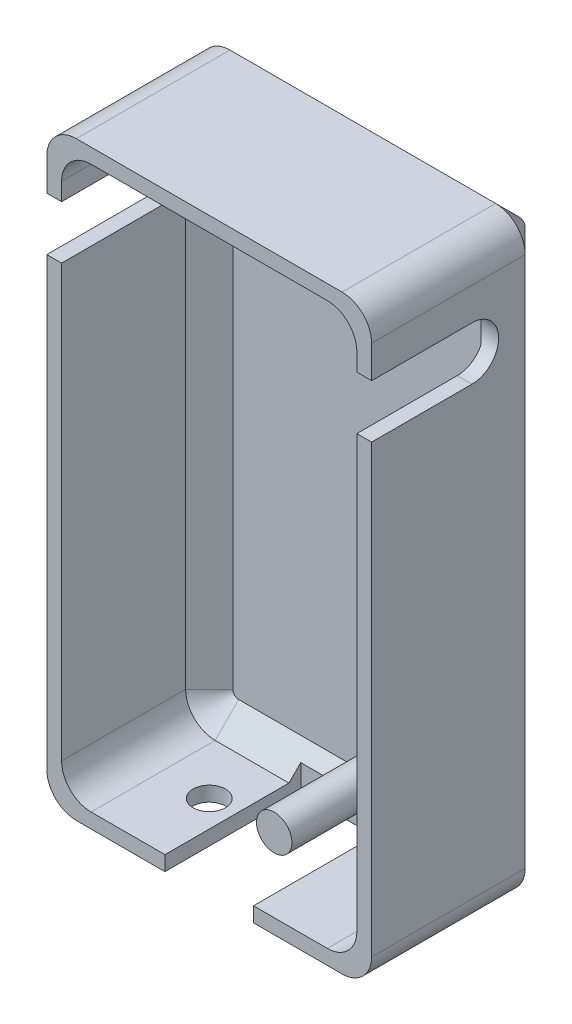
SolidWorks part; units mm, degrees
material "ABS"
ref_plane "前基準面" through (0, 0, 0) normal (0, 0, 1) x (1, 0, 0)
ref_plane "上基準面" through (0, 0, 0) normal (0, 1, 0) x (1, 0, 0)
ref_plane "右基準面" through (0, 0, 0) normal (1, 0, 0) x (0, 0, -1)
sketch "草圖1" plane through (0, 0, 0) normal (0, 0, 1) x (1, 0, 0)
  line L1 (-27.5, -50) -> (27.5, -50)
  line L2 (-27.5, -50) -> (-27.5, 50)
  line L3 (-27.5, 50) -> (27.5, 50)
  line L4 (27.5, -50) -> (27.5, 50)
  line L5 (0, 50) -> (0, -50) construction
  line L6 (-27.5, 0) -> (27.5, 0) construction
  point P0 (0, 0)
  dimension "D1" = 55
  dimension "D2" = 100
extrude "填料-伸長1" add sketch "草圖1" along normal blind 30
sketch "草圖2" plane through (-27.5, 0, 0) normal (-1, 0, 0) x (0, 0, 1)
  line L0 (0, 50) -> (0, -50) construction
  line L2 (13, 30.5) -> (13, 0) construction
  line L3 (13, 0) -> (0, 0) construction
  line L4 (30, 50) -> (30, -50) construction
  line L5 (13, 39.5) -> (30, 39.5)
  line L7 (13, 30.5) -> (30, 30.5)
  line L8 (30, 39.5) -> (30, 30.5)
  arc A0 (13, 39.5) -> (13, 30.5) centre (13, 35) ccw
  dimension "D1" = 9
  dimension "D2" = 13
  dimension "D3" = 35
extrude "除料-伸長1" cut sketch "草圖2" against normal through all
sketch "草圖3" plane through (0, 0, 30) normal (0, 0, 1) x (1, 0, 0)
  line L1 (-25, -47.5) -> (25, -47.5)
  line L2 (-25, -47.5) -> (-25, 47.5)
  line L3 (-25, 47.5) -> (25, 47.5)
  line L4 (25, -47.5) -> (25, 47.5)
  line L5 (0, 47.5) -> (0, -47.5) construction
  line L6 (-25, 0) -> (25, 0) construction
  point P0 (0, 0)
  dimension "D1" = 50
  dimension "D2" = 95
extrude "除料-伸長2" cut sketch "草圖3" against normal blind 25
fillet "圓角1" radius 5 8 edges at (-27.5, -50, 15) (27.5, -50, 15) (-27.5, 50, 15) (27.5, 50, 15) (25, -47.5, 17.5) (-25, -47.5, 17.5) (25, 47.5, 17.5) (-25, 47.5, 17.5)
sketch "草圖5" plane through (0, 0, 5) normal (0, 0, 1) x (1, 0, 0)
  line L0 (0, 0) -> (0, -35) construction
  line L1 (0, -35) -> (11, -35) construction
  line L2 (-22.5, -50) -> (22.5, -50) construction
  circle A0 centre (11, -35) radius 3
  dimension "D2" = 6
  dimension "D1" = 11
  dimension "D3" = 15
extrude "填料-伸長2" add sketch "草圖5" along normal blind 25
sketch "草圖6" plane through (0, -50, 0) normal (0, -1, 0) x (1, 0, 0)
  line L0 (-22.5, 30) -> (22.5, 30) construction
  line L1 (-7.5, 30) -> (7.5, 30)
  line L2 (-7.5, 30) -> (-7.5, 7)
  line L3 (-7.5, 7) -> (7.5, 7)
  line L4 (7.5, 30) -> (7.5, 7)
  line L6 (0, 7) -> (0, 0) construction
  dimension "D1" = 15
  dimension "D2" = 23
extrude "除料-伸長4" cut sketch "草圖6" against normal blind 5
chamfer "導角1" distance 4 angle 45 16 edges at (-27.5, 0, 0) (-26.0355, -48.5355, 0) (-26.0355, 48.5355, 0) (0, -50, 0) (0, 50, 0) (26.0355, -48.5355, 0) (26.0355, 48.5355, 0) (27.5, 0, 0) (-23.5355, -46.0355, 5) (-25, 0, 5) (-23.5355, 46.0355, 5) (0, 47.5, 5) (23.5355, 46.0355, 5) (25, 0, 5) (23.5355, -46.0355, 5) (0, -47.5, 5)
sketch "草圖7" plane through (0, 0, 5) normal (0, 0, 1) x (1, 0, 0)
  circle A0 centre (11, -35) radius 5
  dimension "D1" = 10
extrude "填料-伸長3" add sketch "草圖7" along normal blind 5
sketch "草圖8" plane through (0, -50, 0) normal (0, -1, 0) x (1, 0, 0)
  line L0 (-12, 18) -> (0, 18) construction
  line L1 (0, 18) -> (0, 0) construction
  circle A0 centre (-12, 18) radius 2.75
  dimension "D1" = 5.5
  dimension "D2" = 12
  dimension "D3" = 18
extrude "除料-伸長5" cut sketch "草圖8" against normal blind 5
